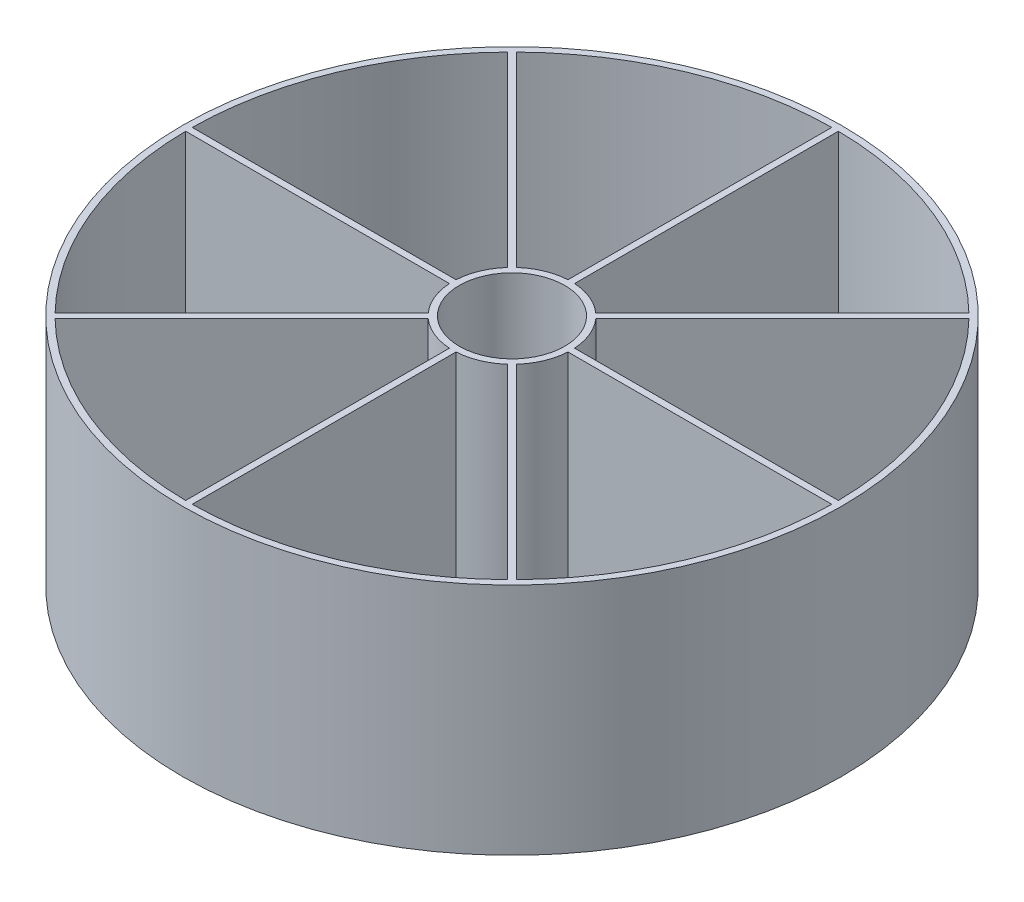
SolidWorks part; units mm, degrees
material "1.4000 (X6Cr13)"
ref_plane "Front Plane" through (0, 0, 0) normal (0, 0, 1) x (1, 0, 0)
ref_plane "Top Plane" through (0, 0, 0) normal (0, 1, 0) x (1, 0, 0)
ref_plane "Right Plane" through (0, 0, 0) normal (1, 0, 0) x (0, 0, -1)
sketch "Sketch1" plane through (0, 0, 0) normal (0, 1, 0) x (1, 0, 0)
  circle A0 centre (0, 0) radius 100
  dimension "D1" = 200
sketch "Sketch2" plane through (0, 0, 0) normal (0, 1, 0) x (1, 0, 0)
  circle A0 centre (0, 0) radius 100
  circle A1 centre (0, 0) radius 98
  dimension "D1" = 196
extrude "Boss-Extrude2" add sketch "Sketch2" along normal blind 70
sketch "Sketch3" plane through (0, 0, 0) normal (0, 1, 0) x (1, 0, 0)
  circle A0 centre (0, 0) radius 18
  circle A1 centre (0, 0) radius 16
  dimension "D1" = 36
  dimension "D2" = 32
extrude "Boss-Extrude3" add sketch "Sketch3" along normal blind 70
sketch "Sketch4" plane through (0, 0, 0) normal (0, 1, 0) x (1, 0, 0)
  line L0 (0, -18) -> (0, -98) construction
  line L1 (-1, -17.9722) -> (-1, -97.9949)
  line L2 (1, -17.9722) -> (1, -97.9949)
  arc A2 (1, -17.9722) -> (-1, -17.9722) centre (0, 0) cw
  arc A3 (1, -97.9949) -> (-1, -97.9949) centre (0, 0) cw
  circle A4 centre (0, 0) radius 18 construction
  circle A5 centre (0, 0) radius 98 construction
  point P2 (0, 0)
  point P3 (0, 0)
  point P5 (0, 0)
  point P15 (0, 0)
  point P17 (0, 0)
  dimension "D1" = 1
  dimension "D2" = 1
extrude "Boss-Extrude4" add sketch "Sketch4" along normal blind 70 contours L0 A2 L1 | L0 A3 L2 region at (0, 0, 57.9945)
pattern_circular "CirPattern1" count 8 over 360 about axis through (0, 70, 0) along (0, -1, 0) of "Boss-Extrude4" reverse direction yes
sketch "Sketch5" plane through (0, 0, 0) normal (0, -1, 0) x (1, 0, 0)
  circle A0 centre (0, 0) radius 100
extrude "Boss-Extrude5" add sketch "Sketch5" along normal blind 1
sketch "Sketch6" plane through (0, 0, 0) normal (0, 1, 0) x (1, 0, 0)
  line L0 (-13.4154, -12.0012) -> (-70, -68.5857) construction
  line L1 (-97.9949, -1) -> (-57.9949, -1)
  line L2 (-17.9722, -1) -> (-97.9949, -1) construction
  line L3 (-70, -68.5857) -> (-41.7157, -40.3015)
  arc A0 (-97.9949, -1) -> (-70, -68.5857) centre (0, 0) ccw
  arc A1 (-57.9949, -1) -> (-41.7157, -40.3015) centre (0, 0) ccw
  point P12 (0, 0)
  dimension "D1" = 40
extrude "Cut-Extrude1" cut sketch "Sketch6" against normal blind 2
pattern_circular "CirPattern2" count 8 over 360 about axis through (0, 70, 0) along (0, -1, 0) of "Cut-Extrude1" reverse direction yes
sketch "Sketch9" plane through (0, 0, 0) normal (0, 1, 0) x (1, 0, 0)
  circle A0 centre (0, 0) radius 16
extrude "Boss-Extrude6" add sketch "Sketch9" along normal blind 10
sketch "Sketch10" plane through (0, 10, 0) normal (0, 1, 0) x (1, 0, 0)
  line L1 (0, 16) -> (-13.8564, 8)
  line L2 (-13.8564, 8) -> (-13.8564, -8)
  line L3 (-13.8564, -8) -> (0, -16)
  line L4 (0, -16) -> (13.8564, -8)
  line L5 (13.8564, -8) -> (13.8564, 8)
  line L6 (13.8564, 8) -> (0, 16)
  circle A0 centre (0, 0) radius 16 construction
extrude "Cut-Extrude2" cut sketch "Sketch10" against normal through all
